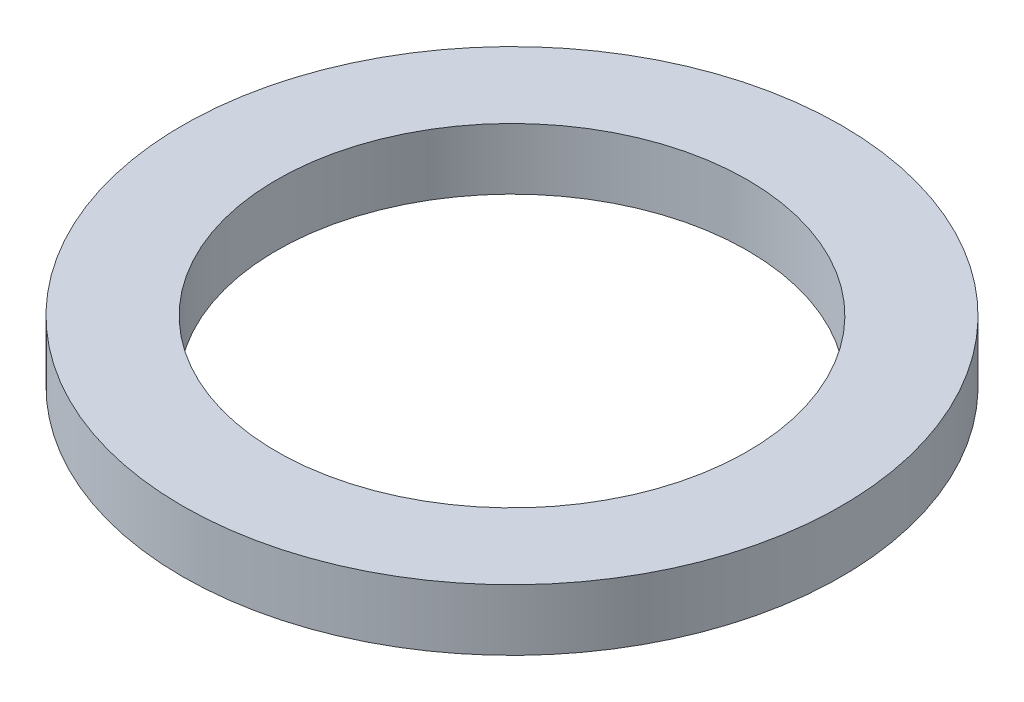
SolidWorks part; units mm, degrees
ref_plane "Front Plane" through (0, 0, 0) normal (0, 0, 1) x (1, 0, 0)
ref_plane "Top Plane" through (0, 0, 0) normal (0, 1, 0) x (1, 0, 0)
ref_plane "Right Plane" through (0, 0, 0) normal (1, 0, 0) x (0, 0, -1)
sketch "Sketch1" plane through (0, 0, 0) normal (0, 1, 0) x (1, 0, 0)
  circle A0 centre (0, 0) radius 70
  dimension "FLANGE_OD" = 140
extrude "Boss-Extrude1" add sketch "Sketch1" along normal blind 13
sketch "Sketch2" plane through (0, 0, 0) normal (0, 1, 0) x (1, 0, 0)
  circle A0 centre (0, 0) radius 50
  dimension "BORE_D" = 100
extrude "Cut-Extrude1" cut sketch "Sketch2" along normal through all
sketch "Sketch3" plane through (0, 13, 0) normal (0, 1, 0) x (1, 0, 0)
  circle A0 centre (0, 0) radius 30.8812 construction
  circle A1 centre (-30.8812, 0) radius 2.6056
  dimension "BOLT_D" = 5.2112
  dimension "BOLT_PCD" = 61.7623
extrude "Cut-Extrude2" cut sketch "Sketch3" against normal blind 9.391 rebuild error yes
pattern_circular "CirPattern1" count 6 over 360 rebuild error yes
